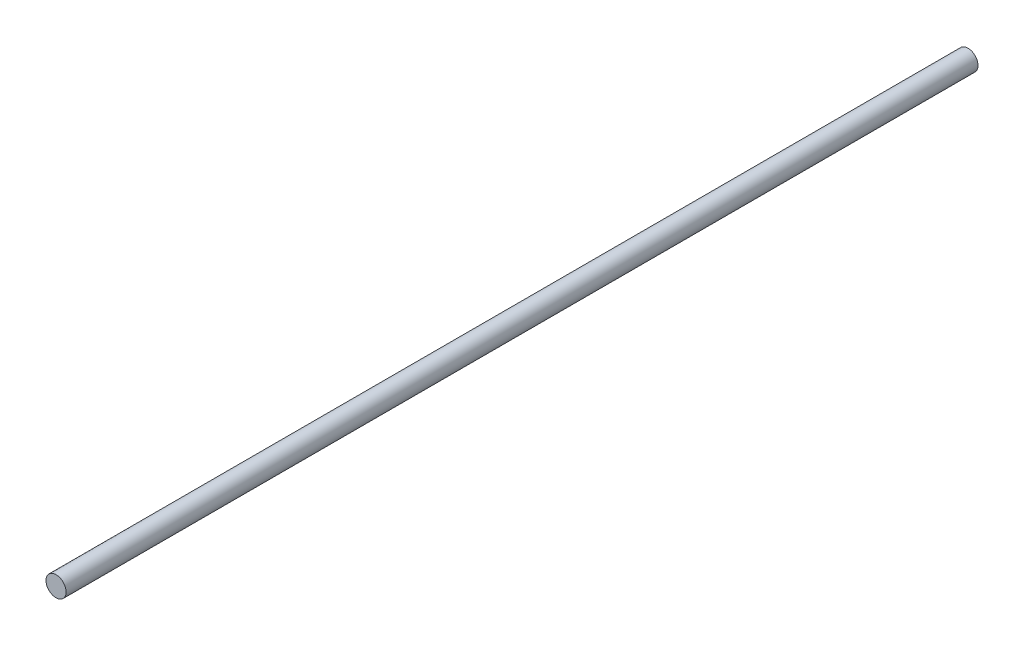
SolidWorks part; units mm, degrees
ref_plane "Front Plane" through (0, 0, 0) normal (0, 0, 1) x (1, 0, 0)
ref_plane "Top Plane" through (0, 0, 0) normal (0, 1, 0) x (1, 0, 0)
ref_plane "Right Plane" through (0, 0, 0) normal (1, 0, 0) x (0, 0, -1)
sketch "Sketch1" plane through (0, 0, 0) normal (0, 0, 1) x (1, 0, 0)
  circle A0 centre (0, 0) radius 9.525
extrude "Boss-Extrude1" add sketch "Sketch1" along normal blind 863.6
